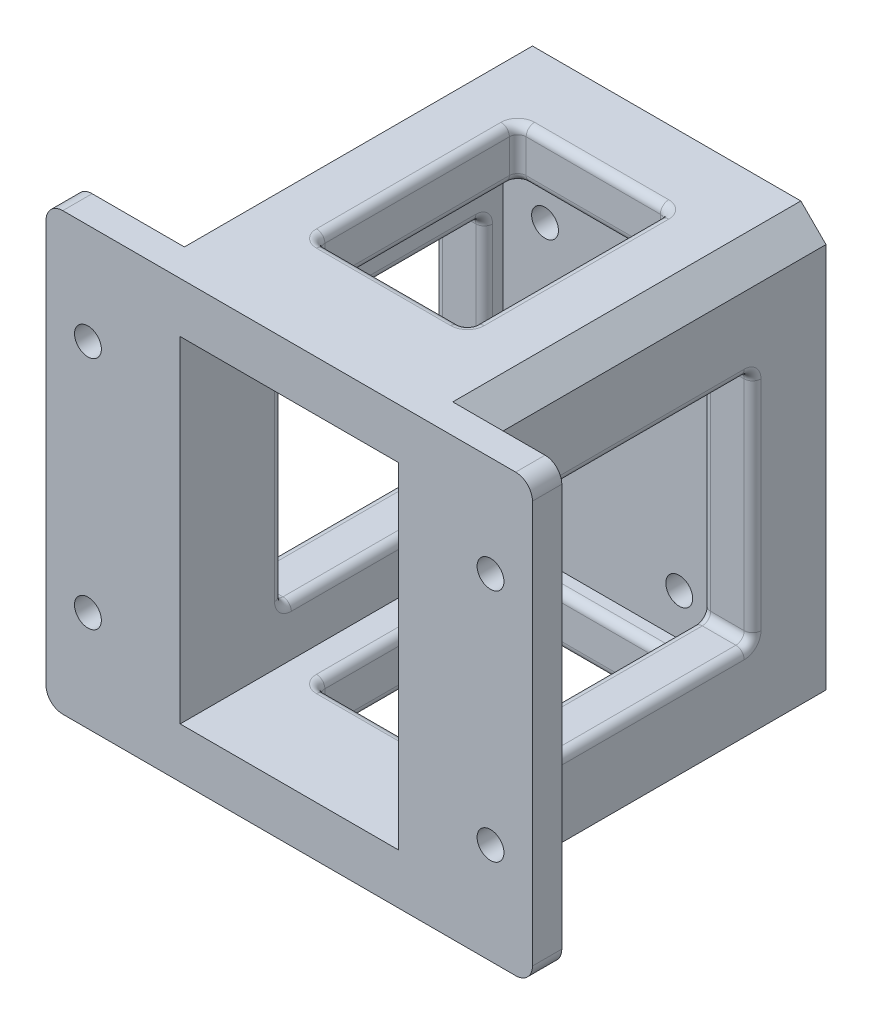
SolidWorks part; units mm, degrees
note: The reader was unsure of these and kept them because the rebuilt part matched: shared geometry of "草图1<3>", "草图1<4>", "草图3<4>", "草图3<5>".
ref_plane "前视基准面" through (0, 0, 0) normal (0, 0, 1) x (1, 0, 0)
ref_plane "上视基准面" through (0, 0, 0) normal (0, 1, 0) x (1, 0, 0)
ref_plane "右视基准面" through (0, 0, 0) normal (1, 0, 0) x (0, 0, -1)
other "Configuration Table"
sketch "草图1" plane through (0, 0, 0) normal (0, 0, 1) x (1, 0, 0)
  line L1 (-14.75, 25.5) -> (11.25, 25.5)
  line L2 (-14.75, 25.5) -> (-14.75, -14.5)
  line L3 (-14.75, -14.5) -> (11.25, -14.5)
  line L4 (11.25, 25.5) -> (11.25, -14.5)
  line L5 (-14.75, 25.5) -> (11.25, -14.5) construction
  line L6 (-14.75, -14.5) -> (11.25, 25.5) construction
  line L7 (-20.75, 31.5) -> (17.25, 31.5)
  line L8 (-20.75, 31.5) -> (-20.75, -20.5)
  line L9 (-20.75, -20.5) -> (17.25, -20.5)
  line L10 (17.25, 31.5) -> (17.25, -20.5)
  line L11 (-20.75, 31.5) -> (17.25, -20.5) construction
  line L12 (-20.75, -20.5) -> (17.25, 31.5) construction
  line L13 (-9.75, 20.5) -> (6.25, 20.5) construction
  line L14 (-9.75, 20.5) -> (-9.75, -9.5) construction
  line L15 (-9.75, -9.5) -> (6.25, -9.5) construction
  line L16 (6.25, 20.5) -> (6.25, -9.5) construction
  line L17 (-9.75, 20.5) -> (6.25, -9.5) construction
  line L18 (-9.75, -9.5) -> (6.25, 20.5) construction
  circle A0 centre (-9.75, 20.5) radius 1.6
  circle A1 centre (6.25, 20.5) radius 1.6
  circle A2 centre (-9.75, -9.5) radius 1.6
  circle A3 centre (6.25, -9.5) radius 1.6
  point P4 (-1.75, 5.5)
  point P9 (-1.75, 5.5)
  point P14 (-1.75, 5.5)
  dimension "D7" = 3.2
  dimension "D1" = 40
  dimension "D2" = 26
  dimension "D3" = 38
  dimension "D4" = 52
  dimension "D5" = 16
  dimension "D6" = 30
  dimension "D8" = 2
  dimension "D9" = 2
extrude "凸台-拉伸1" add sketch "草图1" along normal blind 6.5 contours L2 L3 L4 L1
extrude "切除-拉伸1" cut sketch "草图1<3>" along normal up to next contours A0 | A1 | A3 | A2
sketch "草图1<3>" plane through (0, 0, 0) normal (0, 0, 1) x (1, 0, 0) same geometry as "草图1"
extrude "凸台-拉伸2" add sketch "草图1<4>" along normal blind 45 contours L7 L10 L9 L8 | L4 L3 L2 L1
sketch "草图1<4>" plane through (0, 0, 0) normal (0, 0, 1) x (1, 0, 0) same geometry as "草图1"
sketch "草图3" plane through (0, 0, 45) normal (0, 0, 1) x (1, 0, 0)
  line L0 (-20.75, 31.5) -> (-30.75, 31.5)
  line L1 (-30.75, 31.5) -> (-30.75, -20.5)
  line L2 (-30.75, -20.5) -> (-20.75, -20.5)
  line L3 (-20.75, 31.5) -> (-20.75, -20.5) construction
  line L5 (-1.75, -994.5) -> (-1.75, 49005.5) construction
  line L6 (27.25, -20.5) -> (17.25, -20.5)
  line L7 (17.25, 31.5) -> (27.25, 31.5)
  line L8 (27.25, 31.5) -> (27.25, -20.5)
  circle A0 centre (-25.75, 19.5) radius 1.6
  circle A1 centre (22.25, 19.5) radius 1.6
  circle A2 centre (-25.75, -8.5) radius 1.6
  circle A3 centre (22.25, -8.5) radius 1.6
  dimension "D2" = 3.2
  dimension "D1" = 10
  dimension "D3" = 5
  dimension "D4" = 12
  dimension "D5" = 2
extrude "拉伸-薄壁1" add sketch "草图3" against normal blind 3.5 thin contours L0 L1 L2
extrude "拉伸-薄壁2" add sketch "草图3<4>" against normal blind 3.5 thin contours L7 L8 L6
sketch "草图3<4>" plane through (0, 0, 45) normal (0, 0, 1) x (1, 0, 0) same geometry as "草图3"
extrude "切除-拉伸2" cut sketch "草图3<5>" against normal up to next contours A0 | A2 | A1 | A3
sketch "草图3<5>" plane through (0, 0, 45) normal (0, 0, 1) x (1, 0, 0) same geometry as "草图3"
fillet "圆角1" radius 2 4 edges at (-30.75, 31.5, 43.25) (-30.75, -20.5, 43.25) (27.25, -20.5, 43.25) (27.25, 31.5, 43.25)
chamfer "倒角1" distance 3 angle 45 4 edges at (17.25, 31.5, 20.75) (17.25, -20.5, 20.75) (-20.75, -20.5, 20.75) (-20.75, 31.5, 20.75)
sketch "草图4" plane through (-20.75, 0, 0) normal (-1, 0, 0) x (0, 0, 1)
  line L1 (0, 28.5) -> (41.5, 28.5) construction
  line L2 (0, 28.5) -> (0, -17.5) construction
  line L3 (0, -17.5) -> (41.5, -17.5) construction
  line L4 (41.5, 28.5) -> (41.5, -17.5) construction
  line L5 (0, 28.5) -> (41.5, -17.5) construction
  line L6 (0, -17.5) -> (41.5, 28.5) construction
  line L7 (8.75, 19.5) -> (32.75, 19.5)
  line L8 (8.75, 19.5) -> (8.75, -8.5)
  line L9 (8.75, -8.5) -> (32.75, -8.5)
  line L10 (32.75, 19.5) -> (32.75, -8.5)
  line L11 (8.75, 19.5) -> (32.75, -8.5) construction
  line L12 (8.75, -8.5) -> (32.75, 19.5) construction
  point P4 (20.75, 5.5)
  point P11 (20.75, 5.5)
  dimension "D1" = 24
  dimension "D2" = 28
extrude "切除-拉伸3" cut sketch "草图4" against normal up to next
ref_plane "基准面1" through (-1.75, 0, 0) normal (-1, 0, 0) x (0, 0, 1)
mirror "镜向1" about plane through (-1.75, 0, 0) normal (-1, 0, 0) of "切除-拉伸3"
sketch "草图5" plane through (0, 31.5, 0) normal (0, 1, 0) x (1, 0, 0)
  line L1 (-17.75, 0) -> (14.25, 0) construction
  line L2 (-17.75, 0) -> (-17.75, -41.5) construction
  line L3 (-17.75, -41.5) -> (14.25, -41.5) construction
  line L4 (14.25, 0) -> (14.25, -41.5) construction
  line L5 (-17.75, 0) -> (14.25, -41.5) construction
  line L6 (-17.75, -41.5) -> (14.25, 0) construction
  line L7 (-10.75, -32.75) -> (7.25, -32.75)
  line L8 (-10.75, -32.75) -> (-10.75, -8.75)
  line L9 (-10.75, -8.75) -> (7.25, -8.75)
  line L10 (7.25, -32.75) -> (7.25, -8.75)
  line L11 (-10.75, -32.75) -> (7.25, -8.75) construction
  line L12 (-10.75, -8.75) -> (7.25, -32.75) construction
  point P4 (-1.75, -20.75)
  point P11 (-1.75, -20.75)
  dimension "D1" = 24
  dimension "D2" = 18
extrude "切除-拉伸4" cut sketch "草图5" against normal through all
fillet "圆角2" radius 1 48 edges at (-14.75, 19.5, 20.75) (-14.75, -8.5, 20.75) (-20.75, -8.5, 20.75) (-20.75, 19.5, 20.75) (11.25, 19.5, 20.75) (11.25, -8.5, 20.75) (17.25, -8.5, 20.75) (17.25, 19.5, 20.75) (-14.75, 5.5, 32.75) (-17.75, 19.5, 32.75) (-20.75, 5.5, 32.75) (-17.75, -8.5, 32.75) (-14.75, 5.5, 8.75) (-17.75, -8.5, 8.75) (-20.75, 5.5, 8.75) (-17.75, 19.5, 8.75) (11.25, 5.5, 8.75) (14.25, 19.5, 8.75) (17.25, 5.5, 8.75) (14.25, -8.5, 8.75) (11.25, 5.5, 32.75) (14.25, -8.5, 32.75) (17.25, 5.5, 32.75) (14.25, 19.5, 32.75) (-10.75, -20.5, 20.75) (-10.75, -14.5, 20.75) (7.25, -20.5, 20.75) (7.25, -14.5, 20.75) (7.25, 25.5, 20.75) (-10.75, 25.5, 20.75) (-10.75, 31.5, 20.75) (7.25, 31.5, 20.75) (7.25, -17.5, 8.75) (-1.75, -20.5, 8.75) (-10.75, -17.5, 8.75) (-1.75, -14.5, 8.75) (-10.75, -17.5, 32.75) (-1.75, -20.5, 32.75) (7.25, -17.5, 32.75) (-1.75, -14.5, 32.75) (-1.75, 25.5, 32.75) (7.25, 28.5, 32.75) (-1.75, 31.5, 32.75) (-10.75, 28.5, 32.75) (-1.75, 25.5, 8.75) (-10.75, 28.5, 8.75) (-1.75, 31.5, 8.75) (7.25, 28.5, 8.75)
